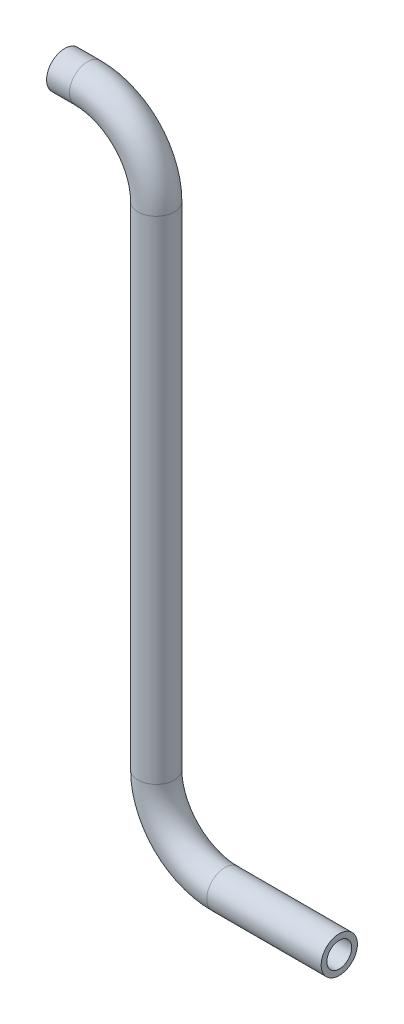
SolidWorks part; units mm, degrees
ref_plane "Piano frontale" through (0, 0, 0) normal (0, 0, 1) x (1, 0, 0)
ref_plane "Piano superiore" through (0, 0, 0) normal (0, 1, 0) x (1, 0, 0)
ref_plane "Piano destro" through (0, 0, 0) normal (1, 0, 0) x (0, 0, -1)
sketch "Schizzo1" plane through (0, 0, 0) normal (0, 0, 1) x (1, 0, 0)
  line L0 (0, 6) -> (0, 49)
  line L1 (-6, 55) -> (-8, 55)
  line L2 (6, 0) -> (16, 0)
  line L3 (-8, 51.696) -> (-8, 71.3288) construction
  arc A0 (0, 49) -> (-6, 55) centre (-6, 49) ccw
  arc A1 (0, 6) -> (6, 0) centre (6, 6) ccw
  point P7 (0, 55)
  point P10 (0, 0)
  point P11 (-10.856, 55)
  point P12 (-11.144, 55)
  point P15 (0, 0)
  point P16 (14.7368, 0)
  point P17 (11.0649, 0.1806)
  dimension "D3" = 6
  dimension "D1" = 55
  dimension "D2" = 10
  dimension "D4" = 90
  dimension "D5" = 90
sweep "Sweep-Sottile1" add path "Schizzo1" circular profile diameter 3.17 parameters "D1"=0.5, "D3"=3.17
